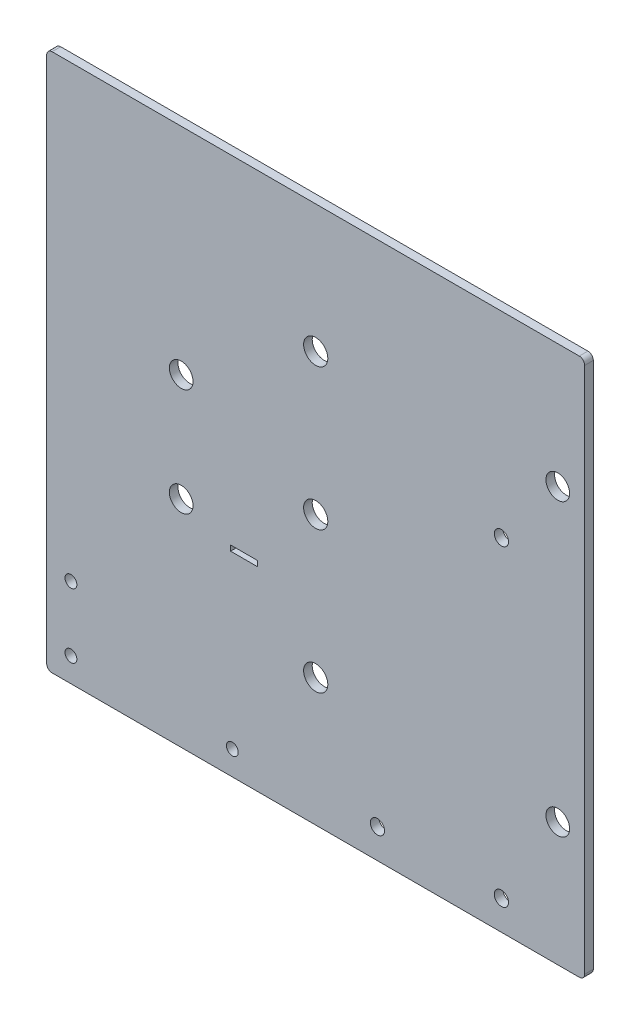
SolidWorks part; units mm, degrees
material "FR4_stuffedProtoboard"
ref_plane "Front Plane" through (0, 0, 0) normal (0, 0, 1) x (1, 0, 0)
ref_plane "Top Plane" through (0, 0, 0) normal (0, 1, 0) x (1, 0, 0)
ref_plane "Right Plane" through (0, 0, 0) normal (1, 0, 0) x (0, 0, -1)
sketch "Sketch1" plane through (0, 0, 0) normal (0, 0, 1) x (1, 0, 0)
  line L1 (-50, -50) -> (50, -50)
  line L2 (-50, -50) -> (-50, 50)
  line L3 (-50, 50) -> (50, 50)
  line L4 (50, -50) -> (50, 50)
  line L5 (-50, -50) -> (50, 50) construction
  line L6 (-50, 50) -> (50, -50) construction
  dimension "D1" = 100
extrude "Boss-Extrude1" add sketch "Sketch1" along normal blind 1.6
sketch "Sketch2" [suppressed] plane through (0, 0, 1.6) normal (0, 0, 1) x (1, 0, 0)
  circle A0 centre (0, 0) radius 50
  line M2 (50, -50) -> (50, 50)
  line M3 (50, 50) -> (-50, 50)
  line M4 (-50, 50) -> (-50, -50)
  line M5 (-50, -50) -> (50, -50)
  dimension "D1" = 100
extrude "Cut-Extrude1" [suppressed] cut sketch "Sketch2" against normal blind 1.6 contours A0 M3 M4 | A0 M4 M5 | A0 M5 M2 | A0 M2 M3
sketch "Sketch3" plane through (0, 0, 0) normal (0, 0, -1) x (-1, 0, 0)
  circle A0 centre (0, 26.25) radius 2.2479 construction
  circle A2 centre (0, 26.25) radius 2.2479
  circle A3 centre (0, 0) radius 2.2479
  circle A4 centre (-34.525, -44.525) radius 1.325 construction
  circle A6 centre (-34.525, -44.525) radius 1.325
  circle A8 centre (0, -26.25) radius 2.2479 construction
  circle A9 centre (0, -26.25) radius 2.2479
  circle A10 centre (-45, -27) radius 2.2 construction
  circle A11 centre (-45, -27) radius 2.2
  circle A12 centre (-45, 27) radius 2.2 construction
  circle A13 centre (-45, 27) radius 2.2
  circle A14 centre (-34.525, 13.525) radius 1.325 construction
  circle A15 centre (-34.525, 13.525) radius 1.325
  circle A16 centre (15.5, -45.5) radius 1.1 construction
  circle A17 centre (15.5, -45.5) radius 1.1
  circle A18 centre (45.5, -45.5) radius 1.1 construction
  circle A19 centre (45.5, -45.5) radius 1.1
  circle A20 centre (45.5, -33.5) radius 1.1 construction
  circle A21 centre (45.5, -33.5) radius 1.1
  circle A22 centre (-11.475, -44.525) radius 1.325 construction
  circle A23 centre (-11.475, -44.525) radius 1.325
  circle A24 centre (25, -10) radius 2.2 construction
  circle A25 centre (25, -10) radius 2.2
  circle A26 centre (25, 10) radius 2.2 construction
  circle A27 centre (25, 10) radius 2.2
  dimension "D1" = 4.4958
extrude "Cut-Extrude2" cut sketch "Sketch3" against normal up to surface (1.6 mm away) up to face at (0, 0, 1.6)
sketch "Sketch4" plane through (0, 0, 1.6) normal (0, 0, 1) x (1, 0, 0)
  line L0 (38, -44.25) -> (38, -18.925) construction
  line L5 (38, -44.25) -> (38, -18.925)
  line L6 (11.75, -48) -> (34.25, -48) construction
  line L7 (11.75, -48) -> (34.25, -48)
  line L8 (8, -44.25) -> (8, 13.25) construction
  line L9 (8, -44.25) -> (8, 13.25)
  line L10 (-13.3154, -13.3154) -> (-13.3154, -28.3154) construction
  line L11 (33, -3) -> (33, -48) construction
  line L13 (34.25, 17) -> (11.75, 17)
  line L14 (38, 13.25) -> (38, -18.925)
  line L15 (-48, -48) -> (-13, -48) construction
  line L16 (-48, -48) -> (-13, -48)
  line L17 (-48, -31) -> (-48, -48) construction
  line L18 (-48, -31) -> (-48, -48)
  line L19 (-13, -40.5) -> (-13, -32.5) construction
  line L20 (-13, -40.5) -> (-13, -32.5)
  line L21 (-13, -48) -> (-13, -40.5) construction
  line L22 (-13, -48) -> (-13, -40.5)
  line L23 (-13, -32.5) -> (-13, -31) construction
  line L24 (-13, -32.5) -> (-13, -31)
  line L25 (-13, -31) -> (-48, -31) construction
  line L26 (-13, -31) -> (-48, -31)
  line L27 (-20, -34) -> (-20, -48) construction
  line L28 (-10.8154, -12.8154) -> (-15.8154, -12.8154)
  line L29 (-10.8154, -12.8154) -> (-10.8154, -13.8154)
  line L30 (-10.8154, -13.8154) -> (-15.8154, -13.8154)
  line L31 (-15.8154, -12.8154) -> (-15.8154, -13.8154)
  line L32 (-10.8154, -12.8154) -> (-15.8154, -13.8154) construction
  line L33 (-10.8154, -13.8154) -> (-15.8154, -12.8154) construction
  arc A0 (34.25, -48) -> (38, -44.25) centre (34.25, -44.25) ccw construction
  arc A1 (34.25, -48) -> (38, -44.25) centre (34.25, -44.25) ccw
  arc A2 (8, -44.25) -> (11.75, -48) centre (11.75, -44.25) ccw construction
  arc A3 (8, -44.25) -> (11.75, -48) centre (11.75, -44.25) ccw
  arc A4 (11.75, 17) -> (8, 13.25) centre (11.75, 13.25) ccw construction
  arc A5 (11.75, 17) -> (8, 13.25) centre (11.75, 13.25) ccw
  arc A6 (38, 13.25) -> (34.25, 17) centre (34.25, 13.25) ccw construction
  arc A7 (38, 13.25) -> (34.25, 17) centre (34.25, 13.25) ccw
  spline S1 degree 3 poles (-620.7454, 1875.7318) (1130.7944, -1753.4911) (-1538.0407, 1395.2657) (1751.4585, -929.0571) knots -44.539328 -44.539328 -44.539328 -44.539328 44.800344 44.800344 44.800344 44.800344 only from (-11.0484, -16.3728) to (-13.3154, -13.3154) construction
  spline S3 degree 3 poles (-13.0064, -13.8154) (-13.1119, -13.6503) (-13.2149, -13.4836) (-13.3154, -13.3154) knots 0.845859 0.845859 0.845859 0.845859 1 1 1 1 construction
  text T0 "Raspberry Pi Zero W" font "Century Gothic" height 2
  text T1 "Atheros" font "Century Gothic" height 2
  text T2 "ANTENNA HOLE" font "Century Gothic" height in points 5
  point P15 (0, 0)
  dimension "D5" = 1
  dimension "D1" = 5
  dimension "D2" = 20
  dimension "D3" = 3
  dimension "D4" = 7
  dimension "D6" = 15
  dimension "D7" = 5
fillet "Fillet1" radius 1 4 edges at (-50, -50, 0.8) (-50, 50, 0.8) (50, -50, 0.8) (50, 50, 0.8)
extrude "Cut-Extrude3" cut sketch "Sketch4" against normal up to surface (1.6 mm away) contours L28 L31 L30 L29 region at (-13.3154, -13.3154, 1.6) up to face at (-46.6, -45.5, 0)
